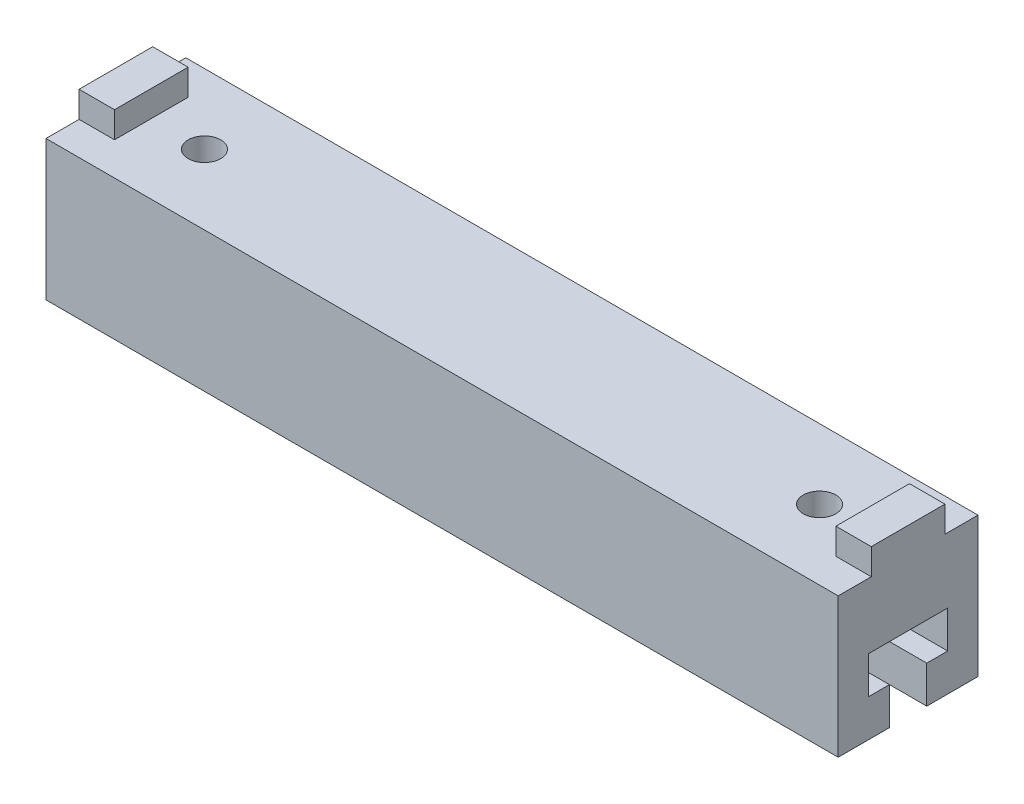
SolidWorks part; units mm, degrees
ref_plane "Front Plane" through (0, 0, 0) normal (0, 0, 1) x (1, 0, 0)
ref_plane "Top Plane" through (0, 0, 0) normal (0, 1, 0) x (1, 0, 0)
ref_plane "Right Plane" through (0, 0, 0) normal (1, 0, 0) x (0, 0, -1)
sketch "Sketch1" plane through (0, 0, 0) normal (0, 1, 0) x (1, 0, 0)
  line L1 (-42.5, -7.5) -> (42.5, -7.5)
  line L2 (-42.5, -7.5) -> (-42.5, 7.5)
  line L3 (-42.5, 7.5) -> (42.5, 7.5)
  line L4 (42.5, -7.5) -> (42.5, 7.5)
  line L5 (0, 7.5) -> (0, -7.5) construction
  line L6 (-42.5, 0) -> (42.5, 0) construction
  point P0 (0, 0)
  dimension "D1" = 15
  dimension "D2" = 85
extrude "Boss-Extrude1" add sketch "Sketch1" along normal blind 15
sketch "Sketch2" plane through (0, 15, 0) normal (0, 1, 0) x (1, 0, 0)
  line L0 (-42.5, 0) -> (42.5, 0) construction
  line L1 (-42.5, 7.5) -> (-42.5, -7.5) construction
  line L2 (42.5, -7.5) -> (42.5, 7.5) construction
  line L3 (0, 0) -> (0, 7.5) construction
  line L4 (-42.5, -3.95) -> (-38.7, -3.95)
  line L5 (-42.5, -3.95) -> (-42.5, 3.95)
  line L6 (-42.5, 3.95) -> (-38.7, 3.95)
  line L7 (-38.7, -3.95) -> (-38.7, 3.95)
  line L8 (42.5, 7.5) -> (-42.5, 7.5) construction
  line L9 (42.5, 3.95) -> (38.7, 3.95)
  line L10 (38.7, -3.95) -> (38.7, 3.95)
  line L11 (42.5, -3.95) -> (38.7, -3.95)
  line L12 (42.5, -3.95) -> (42.5, 3.95)
  point P10 (-42.5, 0)
  dimension "D1" = 7.9
  dimension "D2" = 3.8
extrude "Boss-Extrude2" add sketch "Sketch2" along normal blind 2.8
sketch "Sketch3" plane through (42.5, 0, 0) normal (1, 0, 0) x (0, 0, -1)
  line L0 (-7.5, 0) -> (7.5, 0) construction
  line L1 (-2, 0) -> (2, 0)
  line L2 (-2, 0) -> (-2, 4)
  line L4 (2, 0) -> (2, 4)
  line L5 (3.95, 15) -> (7.5, 15) construction
  line L6 (-4.25, 8) -> (4.25, 8)
  line L7 (-4.25, 8) -> (-4.25, 4)
  line L8 (-4.25, 4) -> (-2, 4)
  line L9 (4.25, 8) -> (4.25, 4)
  line L12 (2, 4) -> (4.25, 4)
  line L14 (0, 8) -> (0, 0) construction
  point P11 (0, 0)
  point P12 (0, 0)
  dimension "D1" = 7
  dimension "D2" = 4
  dimension "D3" = 4
  dimension "D5" = 8.5
extrude "Cut-Extrude2" cut sketch "Sketch3" against normal through all and the other way through all
sketch "Sketch5" plane through (0, 15, 0) normal (0, 1, 0) x (1, 0, 0)
  line L0 (0, 0) -> (-42.8274, 0) construction
  line L1 (0, 0) -> (0, -7.5) construction
  line L2 (-42.5, -7.5) -> (42.5, -7.5) construction
  circle A0 centre (33, 0) radius 1.75
  circle A1 centre (-33, 0) radius 1.75
  dimension "D2" = 3.5
  dimension "D1" = 33
extrude "Cut-Extrude3" cut sketch "Sketch5" against normal through all
